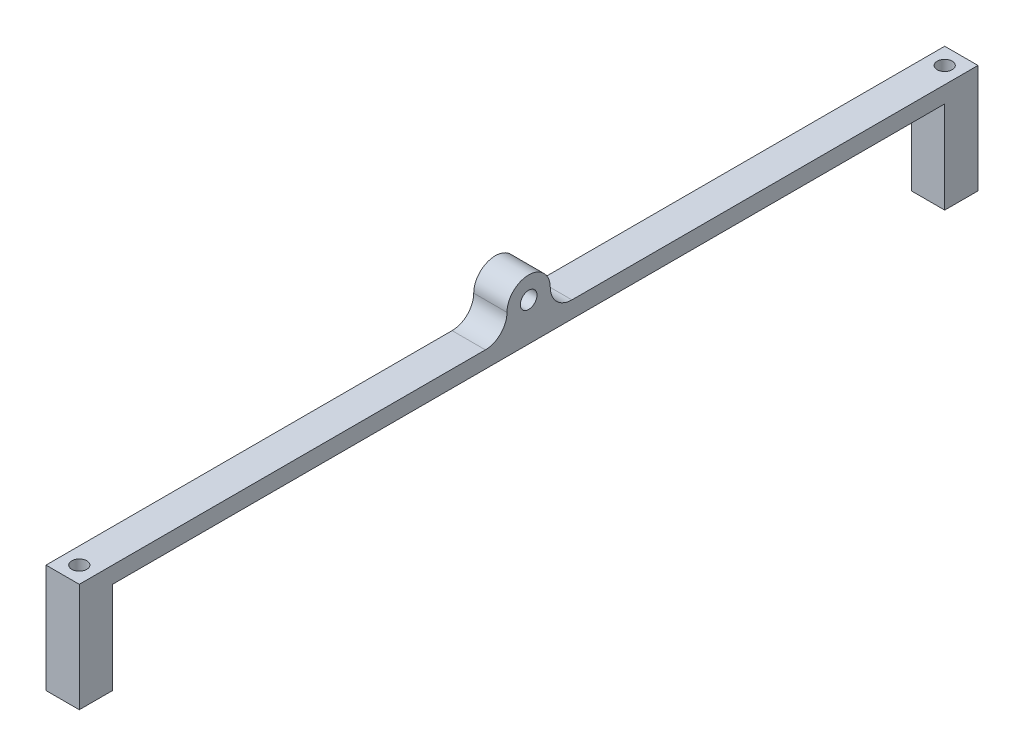
SolidWorks part; units mm, degrees
ref_plane "Спереди" through (0, 0, 0) normal (0, 0, 1) x (1, 0, 0)
ref_plane "Сверху" through (0, 0, 0) normal (0, 1, 0) x (1, 0, 0)
ref_plane "Справа" through (0, 0, 0) normal (1, 0, 0) x (0, 0, -1)
other "Configuration Table"
sketch "Эскиз1" plane through (0, 0, 0) normal (0, 1, 0) x (1, 0, 0)
  line L1 (0, 270) -> (10, 270)
  line L2 (0, 270) -> (0, 0)
  line L3 (0, 0) -> (10, 0)
  line L4 (10, 270) -> (10, 0)
  line L7 (0, 260) -> (10, 270) construction
  line L10 (0, 260) -> (10, 260) construction
  line L14 (0, 10) -> (10, 10) construction
  line L16 (0, 270) -> (10, 260) construction
  line L17 (0, 10) -> (10, 0) construction
  line L18 (10, 10) -> (0, 0) construction
  circle A0 centre (5, 265) radius 2.25
  circle A1 centre (5, 5) radius 2.25
  dimension "Диаметр001" = 4.5
  dimension "Диаметр002" = 4.5
  dimension "X001" = 5
  dimension "X002" = 10
  dimension "Y001" = 5
  dimension "Y003" = 260
  dimension "Y004" = 265
  dimension "Y005" = 270
extrude "Бобышка-Вытянуть1" add sketch "Эскиз1" along normal blind 5
sketch "Эскиз2" plane through (0, 0, 0) normal (1, 0, 0) x (0, 0, -1)
  line L0 (128.5, 11.5) -> (141.5, 11.5) construction
  line L1 (122, 5) -> (148, 5)
  line L2 (0, 5) -> (270, 5) construction
  arc A0 (141.5, 11.5) -> (128.5, 11.5) centre (135, 11.5) ccw
  arc A2 (122, 5) -> (128.5, 11.5) centre (122, 11.5) ccw
  arc A3 (141.5, 11.5) -> (148, 5) centre (148, 11.5) ccw
  circle A4 centre (135, 11.5) radius 2.5
  point P1 (135, 5)
  point P5 (135, 5)
  point P6 (141.5, 11.5)
  point P7 (128.5, 11.5)
  dimension "D1" = 13
  dimension "D2" = 13
  dimension "D3" = 13
  dimension "D4" = 5
extrude "Бобышка-Вытянуть2" add sketch "Эскиз2" along normal blind 10
sketch "Эскиз3" plane through (0, 0, 0) normal (0, -1, 0) x (1, 0, 0)
  line L1 (0, 0) -> (10, 0)
  line L2 (0, 0) -> (0, -10)
  line L3 (0, -10) -> (10, -10)
  line L4 (10, 0) -> (10, -10)
  line L6 (0, -270) -> (10, -270)
  line L7 (0, -270) -> (0, -260)
  line L8 (0, -260) -> (10, -260)
  line L9 (10, -270) -> (10, -260)
  circle A527 centre (5, -265) radius 2.25
  circle A530 centre (5, -5) radius 2.25
  dimension "Диаметр001" = 4.5
  dimension "Диаметр002" = 4.5
  dimension "X001" = 5
  dimension "X002" = 10
  dimension "Y003" = 260
  dimension "Y001" = 270
  dimension "Y002" = 265
  dimension "Y005" = 5
extrude "Бобышка-Вытянуть3" add sketch "Эскиз3" along normal blind 27.65
equation "\"Ширина пластины\" = 50"
equation "\"Ширина ячейки\"= \"Ширина груза\" + 10"
equation "\"Ширина груза\"= 160"
equation "\"Глубина груза\"= 240"
equation "\"Высота груза\"= 160"
equation "\"Глубина ячейки\"= \"Глубина груза\" + 10"
equation "\"Высота ячейки\"= \"Высота груза\" + 10 + 13"
equation "\"Колво ячеек ширина\"= 2"
equation "\"Колво ячеек высота\"= 2"
equation "\"Крепление дверцы\"= 5 "
equation "\"Высота рейки\"= 20"
equation "\"Колво полозьев\"= 5"
equation "\"Отступ рейки\"= 20"
equation "\"Отступ шпильки\"= 26"
equation "\"Диаметр шпильки\"= 5"
equation "\"Колво выгрузки\"= 1"
equation "\"Мотор X ширина корпуса\"= 42.3"
equation "\"Мотор X высота корпуса\"= 42.3"
equation "\"Мотор X длина корпуса\"= 40"
equation "\"Мотор X вылет вала\"= 19.8"
equation "\"Мотор Y ширина корпуса\"= 42.3"
equation "\"Мотор Y высота корпуса\"= 42.3"
equation "\"Мотор Y длина корпуса\"= 48"
equation "\"Мотор Y вылет вала\"= 30"
equation "\"Мотор Z ширина корпуса\"= 42"
equation "\"Мотор Z высота корпуса\"= 42"
equation "\"Мотор Z длина корпуса\"= 40"
equation "\"Мотор Z вылет вала\"= 23"
equation "\"Мотор диаметр вала ПРЕДВ\"= 5"
equation "\"Мотор шаг крепления ПРЕДВ\"= 31"
equation "\"Мотор диаметр отверстий ПРЕДВ\"= 3"
equation "\"Мотор глубина отверстий ПРЕДВ\"= 4.5"
equation "\"Мотор диаметр буртика ПРЕДВ\"= 22"
equation "\"Мотор высота буртика ПРЕДВ\"= 2"
equation "\"Мотор диаметр шкива ПРЕДВ\"= 16"
equation "\"Мотор длина шкива ПРЕДВ\"= 12"
equation "\"Мотор отступ шкива ПРЕДВ\"= 5"
equation "\"Мотор X шаг градусов\"= 1.8"
equation "\"Мотор Y шаг градусов\"= 1.8"
equation "\"Мотор Z шаг градусов\"= 1.8"
equation "\"Мотор Y диаметр ротора\"= 25.78"
equation "\"Толщина шестерни\"= 10"
equation "\"Толщина тонких панелей\" = 6"
equation "\"Толщина вертикальных стенок\" = 6"
equation "\"Толщина горизонтальных плит\" = 6"
equation "\"X001@Эскиз1\" = (4.99999999999998)"
equation "\"X002@Эскиз1\" = (10)"
equation "\"Y001@Эскиз1\" = (5)"
equation "\"Y002@Эскиз1\" = (10)"
equation "\"Y003@Эскиз1\" = (1*(\"Ширина ячейки\"+2*\"Ширина пластины\"-(10)))"
equation "\"Y004@Эскиз1\" = (1*(\"Ширина ячейки\"+2*\"Ширина пластины\"-(5)))"
equation "\"Y005@Эскиз1\" = (1*(\"Ширина ячейки\"+2*\"Ширина пластины\"-(0)))"
equation "\"X001@Эскиз3\" = (4.99999999999999)"
equation "\"X002@Эскиз3\" = (10)"
equation "\"Y001@Эскиз3\" = -(-1*(\"Ширина ячейки\"+2*\"Ширина пластины\"-(0)))"
equation "\"Y002@Эскиз3\" = -(-1*(\"Ширина ячейки\"+2*\"Ширина пластины\"-(5)))"
equation "\"Y003@Эскиз3\" = -(-1*(\"Ширина ячейки\"+2*\"Ширина пластины\"-(10)))"
equation "\"Y004@Эскиз3\" = -(-10)"
equation "\"Y005@Эскиз3\" = -(-5)"
